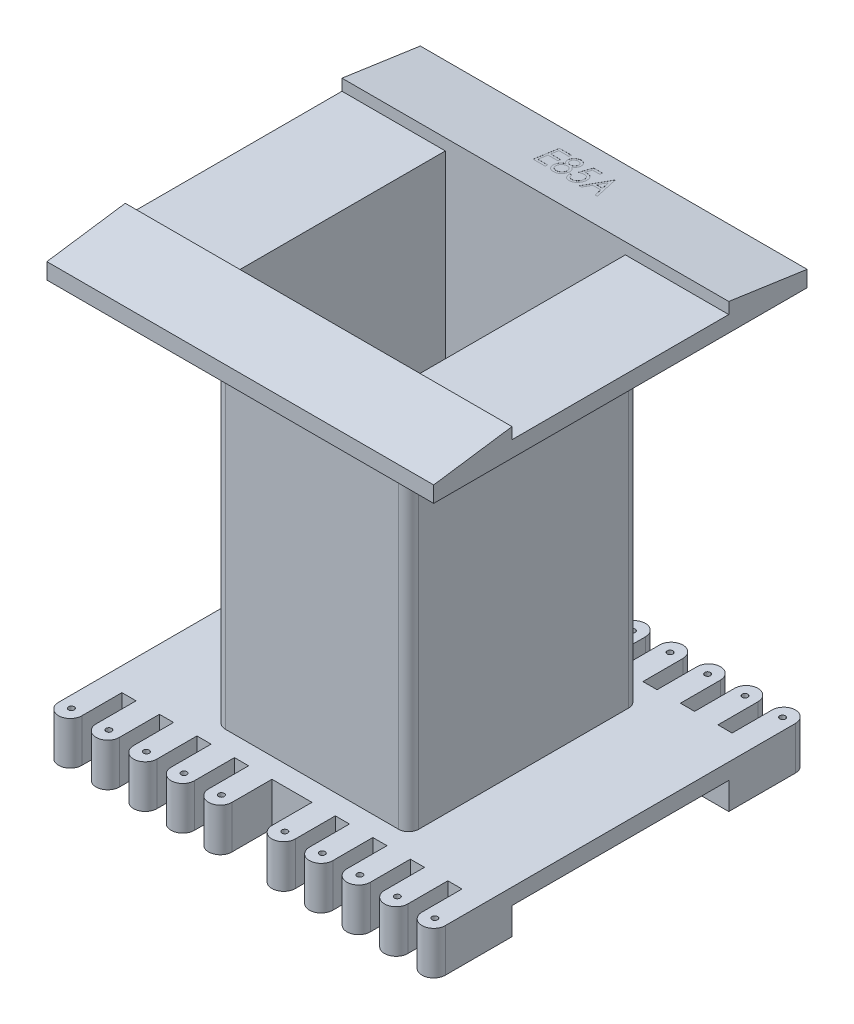
SolidWorks part; units mm, degrees
material "ABS"
ref_plane "Front Plane" through (0, 0, 0) normal (0, 0, 1) x (1, 0, 0)
ref_plane "Top Plane" through (0, 0, 0) normal (0, 1, 0) x (1, 0, 0)
ref_plane "Right Plane" through (0, 0, 0) normal (1, 0, 0) x (0, 0, -1)
sketch "Sketch2" plane through (0, 0, 0) normal (0, 1, 0) x (1, 0, 0)
  line L0 (14.5, -17.25) -> (14.5, 17.25)
  line L5 (13.5, -16.25) -> (-13.5, -16.25)
  line L6 (13.5, -16.25) -> (13.5, 16.25)
  line L11 (13.5, 16.25) -> (-13.5, 16.25)
  line L12 (-13.5, -16.25) -> (-13.5, 16.25)
  line L13 (13.5, -16.25) -> (-13.5, 16.25) construction
  line L14 (13.5, 16.25) -> (-13.5, -16.25) construction
  line L15 (14.5, 17.25) -> (-14.5, 17.25)
  line L16 (-14.5, -17.25) -> (-14.5, 17.25)
  line L17 (14.5, -17.25) -> (-14.5, -17.25)
  point P0 (0, 0)
  point P1 (0, 0)
  point P5 (0, 0)
  dimension "D1" = 32.5
  dimension "D2" = 27
  dimension "D3" = 1
extrude "Boss-Extrude1" add sketch "Sketch2" along normal mid plane 55.7
sketch "Sketch4" plane through (0, 27.85, 0) normal (0, 1, 0) x (1, 0, 0)
  line L1 (-29, -28) -> (29, -28)
  line L2 (-29, -28) -> (-29, 28)
  line L3 (-29, 28) -> (29, 28)
  line L4 (29, -28) -> (29, 28)
  line L5 (-29, -28) -> (29, 28) construction
  line L6 (-29, 28) -> (29, -28) construction
  line L14 (13.5, -16.25) -> (13.5, 16.25) construction
  line L15 (-13.5, -16.25) -> (13.5, -16.25) construction
  line L16 (-13.5, 16.25) -> (-13.5, -16.25) construction
  line L17 (13.5, 16.25) -> (-13.5, 16.25) construction
  line L18 (13.5, -16.25) -> (13.5, 16.25)
  line L19 (-13.5, -16.25) -> (13.5, -16.25)
  line L20 (-13.5, 16.25) -> (-13.5, -16.25)
  line L21 (13.5, 16.25) -> (-13.5, 16.25)
  point P0 (0, 0)
  dimension "D1" = 58
  dimension "D2" = 56
extrude "Boss-Extrude2" add sketch "Sketch4" along normal blind 2.4
mirror "Mirror1" about plane through (0, 0, 0) normal (0, 1, 0) of "Boss-Extrude2"
sketch "Sketch5" plane through (0, 0, 0) normal (1, 0, 0) x (0, 0, -1)
  line L0 (-28, 30.25) -> (-16.25, 31.95)
  line L1 (-16.25, 31.95) -> (-16.25, 30.25)
  line L2 (-28, 30.25) -> (28, 30.25) construction
  line L4 (-16.25, 30.25) -> (-28, 30.25)
  line L5 (0, 0) -> (0, 38.1311) construction
  line L7 (28, 30.25) -> (16.25, 31.95)
  line L8 (16.25, 30.25) -> (28, 30.25)
  line L10 (-16.25, 30.25) -> (-16.25, -30.25) construction
  line L11 (16.25, 31.95) -> (16.25, 30.25)
  dimension "D1" = 1.7
extrude "Boss-Extrude3" add sketch "Sketch5" along normal mid plane 58
sketch "Sketch7" plane through (0, -30.25, 0) normal (0, -1, 0) x (1, 0, 0)
  line L0 (0, 35.9012) -> (0, -6.2706) construction
  line L1 (-29, 28) -> (-29, 26.25)
  line L2 (-29, -28) -> (-29, 28) construction
  line L3 (-29, 28) -> (29, 28) construction
  line L4 (-29, 28) -> (-29, 29.25)
  line L5 (-29, 29.25) -> (29, 29.25)
  line L6 (-14.25, 26.25) -> (-14.25, 20.25)
  line L7 (29, 26.25) -> (-16.1638, 26.25) construction
  line L20 (-25.5, 26.25) -> (-25.5, 20.25)
  line L21 (-25.5, 20.25) -> (-23.375, 20.25)
  line L22 (-23.375, 20.25) -> (-23.375, 26.25)
  line L23 (-23.375, 26.25) -> (-25.5, 26.25) construction
  line L24 (-25.5, 26.25) -> (-29, 26.25) construction
  line L28 (-8.625, 26.25) -> (-8.625, 20.25)
  line L29 (-16.1638, 26.25) -> (-23.375, 26.25) construction
  line L30 (-12.125, 20.25) -> (-12.125, 26.25)
  line L31 (-14.25, 20.25) -> (-12.125, 20.25)
  line L32 (-19.875, 26.25) -> (-19.875, 20.25)
  line L33 (-19.875, 20.25) -> (-17.75, 20.25)
  line L34 (-17.75, 20.25) -> (-17.75, 26.25)
  line L35 (-8.625, 20.25) -> (-6.5, 20.25)
  line L36 (-6.5, 20.25) -> (-6.5, 26.25)
  line L37 (16.1638, 26.25) -> (23.375, 26.25) construction
  line L38 (25.5, 26.25) -> (29, 26.25) construction
  line L39 (23.375, 26.25) -> (25.5, 26.25) construction
  line L40 (6.5, 20.25) -> (6.5, 26.25)
  line L41 (8.625, 20.25) -> (6.5, 20.25)
  line L42 (17.75, 20.25) -> (17.75, 26.25)
  line L43 (19.875, 20.25) -> (17.75, 20.25)
  line L44 (19.875, 26.25) -> (19.875, 20.25)
  line L45 (14.25, 20.25) -> (12.125, 20.25)
  line L46 (12.125, 20.25) -> (12.125, 26.25)
  line L47 (8.625, 26.25) -> (8.625, 20.25)
  line L48 (23.375, 20.25) -> (23.375, 26.25)
  line L49 (25.5, 20.25) -> (23.375, 20.25)
  line L50 (25.5, 26.25) -> (25.5, 20.25)
  line L51 (14.25, 26.25) -> (14.25, 20.25)
  line L53 (29, 29.25) -> (29, 26.25)
  line L55 (-3, 26.25) -> (-3, 20.25)
  line L56 (-3, 20.25) -> (3, 20.25)
  line L57 (3, 20.25) -> (3, 26.25)
  line L58 (-27.25, 26.5) -> (-26.02, 26.5) construction
  line L61 (0, 0) -> (-5.5861, 0) construction
  line L62 (-27.25, -26.5) -> (-26.02, -26.5) construction
  line L63 (23.375, -26.25) -> (25.5, -26.25) construction
  line L64 (25.5, -26.25) -> (29, -26.25) construction
  line L65 (16.1638, -26.25) -> (23.375, -26.25) construction
  line L66 (-16.1637, -26.25) -> (-23.375, -26.25) construction
  line L67 (-25.5, -26.25) -> (-29, -26.25) construction
  line L68 (-23.375, -26.25) -> (-25.5, -26.25) construction
  line L69 (29, -26.25) -> (-16.1637, -26.25) construction
  line L70 (3, -20.25) -> (3, -26.25)
  line L71 (-3, -20.25) -> (3, -20.25)
  line L72 (-3, -26.25) -> (-3, -20.25)
  line L73 (29, -29.25) -> (29, -26.25)
  line L74 (14.25, -26.25) -> (14.25, -20.25)
  line L75 (25.5, -26.25) -> (25.5, -20.25)
  line L76 (25.5, -20.25) -> (23.375, -20.25)
  line L77 (23.375, -20.25) -> (23.375, -26.25)
  line L78 (8.625, -26.25) -> (8.625, -20.25)
  line L79 (12.125, -20.25) -> (12.125, -26.25)
  line L80 (14.25, -20.25) -> (12.125, -20.25)
  line L81 (19.875, -26.25) -> (19.875, -20.25)
  line L82 (19.875, -20.25) -> (17.75, -20.25)
  line L83 (17.75, -20.25) -> (17.75, -26.25)
  line L84 (8.625, -20.25) -> (6.5, -20.25)
  line L85 (6.5, -20.25) -> (6.5, -26.25)
  line L86 (-6.5, -20.25) -> (-6.5, -26.25)
  line L87 (-8.625, -20.25) -> (-6.5, -20.25)
  line L88 (-17.75, -20.25) -> (-17.75, -26.25)
  line L89 (-19.875, -20.25) -> (-17.75, -20.25)
  line L90 (-19.875, -26.25) -> (-19.875, -20.25)
  line L91 (-14.25, -20.25) -> (-12.125, -20.25)
  line L92 (-12.125, -20.25) -> (-12.125, -26.25)
  line L93 (-8.625, -26.25) -> (-8.625, -20.25)
  line L94 (-23.375, -20.25) -> (-23.375, -26.25)
  line L95 (-25.5, -20.25) -> (-23.375, -20.25)
  line L96 (-25.5, -26.25) -> (-25.5, -20.25)
  line L97 (-14.25, -26.25) -> (-14.25, -20.25)
  line L98 (-29, -29.25) -> (29, -29.25)
  line L99 (-29, -28) -> (-29, -29.25)
  line L100 (-29, -28) -> (-29, -26.25)
  arc A0 (-29, 26.25) -> (-25.5, 26.25) centre (-27.25, 26.25) cw
  arc A11 (-23.375, 26.25) -> (-19.875, 26.25) centre (-21.625, 26.25) cw
  arc A12 (-17.75, 26.25) -> (-14.25, 26.25) centre (-16, 26.25) cw
  arc A13 (-12.125, 26.25) -> (-8.625, 26.25) centre (-10.375, 26.25) cw
  arc A14 (-6.5, 26.25) -> (-3, 26.25) centre (-4.75, 26.25) cw
  arc A15 (6.5, 26.25) -> (3, 26.25) centre (4.75, 26.25) ccw
  arc A16 (12.125, 26.25) -> (8.625, 26.25) centre (10.375, 26.25) ccw
  arc A17 (17.75, 26.25) -> (14.25, 26.25) centre (16, 26.25) ccw
  arc A18 (23.375, 26.25) -> (19.875, 26.25) centre (21.625, 26.25) ccw
  arc A19 (29, 26.25) -> (25.5, 26.25) centre (27.25, 26.25) ccw
  circle A20 centre (-27.25, 26.075) radius 0.425
  circle A21 centre (-21.625, 26.075) radius 0.425
  circle A22 centre (-16, 26.075) radius 0.425
  circle A23 centre (-10.375, 26.075) radius 0.425
  circle A24 centre (-4.75, 26.075) radius 0.425
  circle A25 centre (21.625, 26.075) radius 0.425
  circle A26 centre (16, 26.075) radius 0.425
  circle A27 centre (10.375, 26.075) radius 0.425
  circle A28 centre (4.75, 26.075) radius 0.425
  circle A29 centre (27.25, 26.075) radius 0.425
  circle A30 centre (27.25, -26.075) radius 0.425
  circle A31 centre (4.75, -26.075) radius 0.425
  circle A32 centre (10.375, -26.075) radius 0.425
  circle A33 centre (16, -26.075) radius 0.425
  circle A34 centre (21.625, -26.075) radius 0.425
  circle A35 centre (-4.75, -26.075) radius 0.425
  circle A36 centre (-10.375, -26.075) radius 0.425
  circle A37 centre (-16, -26.075) radius 0.425
  circle A38 centre (-21.625, -26.075) radius 0.425
  circle A39 centre (-27.25, -26.075) radius 0.425
  arc A40 (29, -26.25) -> (25.5, -26.25) centre (27.25, -26.25) cw
  arc A41 (23.375, -26.25) -> (19.875, -26.25) centre (21.625, -26.25) cw
  arc A42 (17.75, -26.25) -> (14.25, -26.25) centre (16, -26.25) cw
  arc A43 (12.125, -26.25) -> (8.625, -26.25) centre (10.375, -26.25) cw
  arc A44 (6.5, -26.25) -> (3, -26.25) centre (4.75, -26.25) cw
  arc A45 (-6.5, -26.25) -> (-3, -26.25) centre (-4.75, -26.25) ccw
  arc A46 (-12.125, -26.25) -> (-8.625, -26.25) centre (-10.375, -26.25) ccw
  arc A47 (-17.75, -26.25) -> (-14.25, -26.25) centre (-16, -26.25) ccw
  arc A48 (-23.375, -26.25) -> (-19.875, -26.25) centre (-21.625, -26.25) ccw
  arc A49 (-29, -26.25) -> (-25.5, -26.25) centre (-27.25, -26.25) ccw
  dimension "D1" = 1.5
  dimension "D6" = 1.25
  dimension "D8" = 0.85
  dimension "D3" = 9
  dimension "D4" = 6
  dimension "D5" = 2.125
  dimension "D7" = 2
  dimension "D9" = 5
extrude "Cut-Extrude1" cut sketch "Sketch7" against normal blind 3
sketch "Sketch8" plane through (0, -30.25, 0) normal (0, -1, 0) x (1, 0, 0)
  line L0 (-29, 16.25) -> (29, 16.25)
  line L1 (29, 26.25) -> (29, -26.25) construction
  line L2 (0, 0) -> (-9.975, 0) construction
  line L37 (-13.5, 16.25) -> (-29, 16.25) construction
  line L38 (-25.5, -20.25) -> (-25.5, -26.25)
  line L39 (-23.375, -20.25) -> (-25.5, -20.25)
  line L40 (-23.375, -26.25) -> (-23.375, -20.25)
  line L41 (-19.875, -20.25) -> (-19.875, -26.25)
  line L42 (25.5, 26.25) -> (25.5, 20.25)
  line L44 (25.5, 26.25) -> (25.5, 20.25)
  line L45 (25.5, 20.25) -> (23.375, 20.25)
  line L46 (-17.75, -20.25) -> (-19.875, -20.25)
  line L47 (-17.75, -26.25) -> (-17.75, -20.25)
  line L48 (-14.25, -20.25) -> (-14.25, -26.25)
  line L49 (-12.125, -20.25) -> (-14.25, -20.25)
  line L50 (-12.125, -26.25) -> (-12.125, -20.25)
  line L51 (-8.625, -20.25) -> (-8.625, -26.25)
  line L52 (-6.5, -20.25) -> (-8.625, -20.25)
  line L53 (-6.5, -26.25) -> (-6.5, -20.25)
  line L54 (-3, -20.25) -> (-3, -26.25)
  line L55 (3, -20.25) -> (-3, -20.25)
  line L56 (3, -26.25) -> (3, -20.25)
  line L57 (6.5, -20.25) -> (6.5, -26.25)
  line L58 (29, -26.25) -> (29, 26.25)
  line L59 (8.625, -20.25) -> (6.5, -20.25)
  line L60 (8.625, -26.25) -> (8.625, -20.25)
  line L61 (12.125, -20.25) -> (12.125, -26.25)
  line L62 (14.25, -20.25) -> (12.125, -20.25)
  line L63 (14.25, -26.25) -> (14.25, -20.25)
  line L64 (17.75, -20.25) -> (17.75, -26.25)
  line L65 (19.875, -20.25) -> (17.75, -20.25)
  line L66 (19.875, -26.25) -> (19.875, -20.25)
  line L67 (23.375, -20.25) -> (23.375, -26.25)
  line L68 (25.5, -20.25) -> (23.375, -20.25)
  line L69 (-29, -26.25) -> (-29, -16.25)
  line L70 (29, -16.25) -> (29, -26.25)
  line L71 (25.5, -26.25) -> (25.5, -20.25)
  line L72 (-29, -16.25) -> (29, -16.25)
  line L86 (-29, 26.25) -> (-29, -26.25)
  line L114 (29, 16.25) -> (29, 26.25)
  line L142 (-29, 26.25) -> (-29, 16.25)
  line L147 (25.5, 20.25) -> (23.375, 20.25)
  line L148 (23.375, 20.25) -> (23.375, 26.25)
  line L149 (23.375, 20.25) -> (23.375, 26.25)
  line L150 (19.875, 26.25) -> (19.875, 20.25)
  line L151 (19.875, 26.25) -> (19.875, 20.25)
  line L152 (19.875, 20.25) -> (17.75, 20.25)
  line L153 (19.875, 20.25) -> (17.75, 20.25)
  line L154 (17.75, 20.25) -> (17.75, 26.25)
  line L155 (17.75, 20.25) -> (17.75, 26.25)
  line L156 (14.25, 26.25) -> (14.25, 20.25)
  line L157 (14.25, 26.25) -> (14.25, 20.25)
  line L158 (14.25, 20.25) -> (12.125, 20.25)
  line L159 (14.25, 20.25) -> (12.125, 20.25)
  line L160 (12.125, 20.25) -> (12.125, 26.25)
  line L161 (12.125, 20.25) -> (12.125, 26.25)
  line L162 (8.625, 26.25) -> (8.625, 20.25)
  line L163 (8.625, 26.25) -> (8.625, 20.25)
  line L164 (8.625, 20.25) -> (6.5, 20.25)
  line L165 (8.625, 20.25) -> (6.5, 20.25)
  line L166 (6.5, 20.25) -> (6.5, 26.25)
  line L167 (6.5, 20.25) -> (6.5, 26.25)
  line L168 (3, 26.25) -> (3, 20.25)
  line L169 (3, 26.25) -> (3, 20.25)
  line L170 (3, 20.25) -> (-3, 20.25)
  line L171 (3, 20.25) -> (-3, 20.25)
  line L172 (-3, 20.25) -> (-3, 26.25)
  line L173 (-3, 20.25) -> (-3, 26.25)
  line L174 (-6.5, 26.25) -> (-6.5, 20.25)
  line L175 (-6.5, 26.25) -> (-6.5, 20.25)
  line L176 (-6.5, 20.25) -> (-8.625, 20.25)
  line L177 (-6.5, 20.25) -> (-8.625, 20.25)
  line L178 (-8.625, 20.25) -> (-8.625, 26.25)
  line L179 (-8.625, 20.25) -> (-8.625, 26.25)
  line L180 (-12.125, 26.25) -> (-12.125, 20.25)
  line L181 (-12.125, 26.25) -> (-12.125, 20.25)
  line L182 (-12.125, 20.25) -> (-14.25, 20.25)
  line L183 (-12.125, 20.25) -> (-14.25, 20.25)
  line L184 (-14.25, 20.25) -> (-14.25, 26.25)
  line L185 (-14.25, 20.25) -> (-14.25, 26.25)
  line L186 (-17.75, 26.25) -> (-17.75, 20.25)
  line L187 (-17.75, 26.25) -> (-17.75, 20.25)
  line L188 (-17.75, 20.25) -> (-19.875, 20.25)
  line L189 (-17.75, 20.25) -> (-19.875, 20.25)
  line L190 (-19.875, 20.25) -> (-19.875, 26.25)
  line L191 (-19.875, 20.25) -> (-19.875, 26.25)
  line L192 (-23.375, 26.25) -> (-23.375, 20.25)
  line L193 (-23.375, 26.25) -> (-23.375, 20.25)
  line L194 (-23.375, 20.25) -> (-25.5, 20.25)
  line L195 (-23.375, 20.25) -> (-25.5, 20.25)
  line L196 (-25.5, 20.25) -> (-25.5, 26.25)
  line L197 (-25.5, 20.25) -> (-25.5, 26.25)
  line L198 (-25.5, -26.25) -> (-25.5, -20.25)
  line L199 (-25.5, -20.25) -> (-23.375, -20.25)
  line L200 (-23.375, -20.25) -> (-23.375, -26.25)
  line L201 (-19.875, -26.25) -> (-19.875, -20.25)
  line L202 (-19.875, -20.25) -> (-17.75, -20.25)
  line L203 (-17.75, -20.25) -> (-17.75, -26.25)
  line L204 (-14.25, -26.25) -> (-14.25, -20.25)
  line L205 (-14.25, -20.25) -> (-12.125, -20.25)
  line L206 (-12.125, -20.25) -> (-12.125, -26.25)
  line L207 (-8.625, -26.25) -> (-8.625, -20.25)
  line L208 (-8.625, -20.25) -> (-6.5, -20.25)
  line L209 (-6.5, -20.25) -> (-6.5, -26.25)
  line L210 (-3, -26.25) -> (-3, -20.25)
  line L211 (-3, -20.25) -> (3, -20.25)
  line L212 (3, -20.25) -> (3, -26.25)
  line L213 (6.5, -26.25) -> (6.5, -20.25)
  line L214 (6.5, -20.25) -> (8.625, -20.25)
  line L215 (8.625, -20.25) -> (8.625, -26.25)
  line L216 (12.125, -26.25) -> (12.125, -20.25)
  line L217 (12.125, -20.25) -> (14.25, -20.25)
  line L218 (14.25, -20.25) -> (14.25, -26.25)
  line L219 (17.75, -26.25) -> (17.75, -20.25)
  line L220 (17.75, -20.25) -> (19.875, -20.25)
  line L221 (19.875, -20.25) -> (19.875, -26.25)
  line L222 (23.375, -26.25) -> (23.375, -20.25)
  line L223 (23.375, -20.25) -> (25.5, -20.25)
  line L224 (25.5, -20.25) -> (25.5, -26.25)
  arc A10 (-25.5, -26.25) -> (-29, -26.25) centre (-27.25, -26.25) cw
  arc A11 (-19.875, -26.25) -> (-23.375, -26.25) centre (-21.625, -26.25) cw
  arc A12 (-14.25, -26.25) -> (-17.75, -26.25) centre (-16, -26.25) cw
  arc A13 (-8.625, -26.25) -> (-12.125, -26.25) centre (-10.375, -26.25) cw
  arc A14 (-3, -26.25) -> (-6.5, -26.25) centre (-4.75, -26.25) cw
  arc A15 (6.5, -26.25) -> (3, -26.25) centre (4.75, -26.25) cw
  arc A16 (12.125, -26.25) -> (8.625, -26.25) centre (10.375, -26.25) cw
  arc A17 (17.75, -26.25) -> (14.25, -26.25) centre (16, -26.25) cw
  arc A18 (23.375, -26.25) -> (19.875, -26.25) centre (21.625, -26.25) cw
  arc A19 (29, -26.25) -> (25.5, -26.25) centre (27.25, -26.25) cw
  arc A51 (25.5, -26.25) -> (29, -26.25) centre (27.25, -26.25) ccw
  arc A52 (29, 26.25) -> (25.5, 26.25) centre (27.25, 26.25) ccw
  arc A53 (29, 26.25) -> (25.5, 26.25) centre (27.25, 26.25) ccw
  arc A54 (23.375, 26.25) -> (19.875, 26.25) centre (21.625, 26.25) ccw
  arc A55 (23.375, 26.25) -> (19.875, 26.25) centre (21.625, 26.25) ccw
  arc A56 (17.75, 26.25) -> (14.25, 26.25) centre (16, 26.25) ccw
  arc A57 (17.75, 26.25) -> (14.25, 26.25) centre (16, 26.25) ccw
  arc A58 (12.125, 26.25) -> (8.625, 26.25) centre (10.375, 26.25) ccw
  arc A59 (12.125, 26.25) -> (8.625, 26.25) centre (10.375, 26.25) ccw
  arc A60 (6.5, 26.25) -> (3, 26.25) centre (4.75, 26.25) ccw
  arc A61 (6.5, 26.25) -> (3, 26.25) centre (4.75, 26.25) ccw
  arc A62 (-3, 26.25) -> (-6.5, 26.25) centre (-4.75, 26.25) ccw
  arc A63 (-3, 26.25) -> (-6.5, 26.25) centre (-4.75, 26.25) ccw
  arc A64 (-8.625, 26.25) -> (-12.125, 26.25) centre (-10.375, 26.25) ccw
  arc A65 (-8.625, 26.25) -> (-12.125, 26.25) centre (-10.375, 26.25) ccw
  arc A66 (-14.25, 26.25) -> (-17.75, 26.25) centre (-16, 26.25) ccw
  arc A67 (-14.25, 26.25) -> (-17.75, 26.25) centre (-16, 26.25) ccw
  arc A68 (-19.875, 26.25) -> (-23.375, 26.25) centre (-21.625, 26.25) ccw
  arc A69 (-19.875, 26.25) -> (-23.375, 26.25) centre (-21.625, 26.25) ccw
  arc A70 (-25.5, 26.25) -> (-29, 26.25) centre (-27.25, 26.25) ccw
  arc A71 (-25.5, 26.25) -> (-29, 26.25) centre (-27.25, 26.25) ccw
  arc A72 (-29, -26.25) -> (-25.5, -26.25) centre (-27.25, -26.25) ccw
  arc A73 (-23.375, -26.25) -> (-19.875, -26.25) centre (-21.625, -26.25) ccw
  arc A74 (-17.75, -26.25) -> (-14.25, -26.25) centre (-16, -26.25) ccw
  arc A75 (-12.125, -26.25) -> (-8.625, -26.25) centre (-10.375, -26.25) ccw
  arc A76 (-6.5, -26.25) -> (-3, -26.25) centre (-4.75, -26.25) ccw
  arc A77 (3, -26.25) -> (6.5, -26.25) centre (4.75, -26.25) ccw
  arc A78 (8.625, -26.25) -> (12.125, -26.25) centre (10.375, -26.25) ccw
  arc A79 (14.25, -26.25) -> (17.75, -26.25) centre (16, -26.25) ccw
  arc A80 (19.875, -26.25) -> (23.375, -26.25) centre (21.625, -26.25) ccw
  dimension "D1" = 0
extrude "Boss-Extrude4" add sketch "Sketch8" along normal blind 4.05
sketch "Sketch9" plane through (0, 33.5978, -4.861) normal (0, 0.9897, -0.1432) x (1, 0, 0)
  line L0 (-29, 16.0076) -> (29, 16.0076) construction
  line L1 (-29, 23.38) -> (-29, 11.5076) construction
  line L2 (29, 23.38) -> (29, 11.5076) construction
  line L4 (29, 11.5076) -> (-29, 11.5076) construction
  text T0 "E85A" font "Century Gothic" height 4
  dimension "D1" = 4.5
extrude "Cut-Extrude2" cut sketch "Sketch9" against normal blind 0.01
sketch "Sketch10" plane through (0, -27.85, 0) normal (0, 1, 0) x (1, 0, 0)
  circle A0 centre (27.25, -26.075) radius 0.425 construction
  circle A1 centre (21.625, -26.075) radius 0.425 construction
  circle A2 centre (16, -26.075) radius 0.425 construction
  circle A3 centre (10.375, -26.075) radius 0.425 construction
  circle A4 centre (4.75, -26.075) radius 0.425 construction
  circle A5 centre (-4.75, -26.075) radius 0.425 construction
  circle A6 centre (-10.375, -26.075) radius 0.425 construction
  circle A7 centre (-16, -26.075) radius 0.425 construction
  circle A8 centre (-21.625, -26.075) radius 0.425 construction
  circle A9 centre (-27.25, -26.075) radius 0.425 construction
  circle A10 centre (27.25, 26.075) radius 0.425 construction
  circle A11 centre (21.625, 26.075) radius 0.425 construction
  circle A12 centre (16, 26.075) radius 0.425 construction
  circle A13 centre (10.375, 26.075) radius 0.425 construction
  circle A14 centre (4.75, 26.075) radius 0.425 construction
  circle A15 centre (-4.75, 26.075) radius 0.425 construction
  circle A16 centre (-10.375, 26.075) radius 0.425 construction
  circle A17 centre (-16, 26.075) radius 0.425 construction
  circle A18 centre (-21.625, 26.075) radius 0.425 construction
  circle A19 centre (-27.25, 26.075) radius 0.425 construction
  circle A20 centre (27.25, -26.075) radius 0.425
  circle A21 centre (21.625, -26.075) radius 0.425
  circle A22 centre (16, -26.075) radius 0.425
  circle A23 centre (10.375, -26.075) radius 0.425
  circle A24 centre (4.75, -26.075) radius 0.425
  circle A25 centre (-4.75, -26.075) radius 0.425
  circle A26 centre (-10.375, -26.075) radius 0.425
  circle A27 centre (-16, -26.075) radius 0.425
  circle A28 centre (-21.625, -26.075) radius 0.425
  circle A29 centre (-27.25, -26.075) radius 0.425
  circle A30 centre (27.25, 26.075) radius 0.425
  circle A31 centre (21.625, 26.075) radius 0.425
  circle A32 centre (16, 26.075) radius 0.425
  circle A33 centre (10.375, 26.075) radius 0.425
  circle A34 centre (4.75, 26.075) radius 0.425
  circle A35 centre (-4.75, 26.075) radius 0.425
  circle A36 centre (-10.375, 26.075) radius 0.425
  circle A37 centre (-16, 26.075) radius 0.425
  circle A38 centre (-21.625, 26.075) radius 0.425
  circle A39 centre (-27.25, 26.075) radius 0.425
extrude "Cut-Extrude3" cut sketch "Sketch10" against normal blind 10
fillet "Fillet1" radius 1.5 4 edges at (-14.5, 0, 17.25) (-14.5, 0, -17.25) (14.5, 0, -17.25) (14.5, 0, 17.25)
